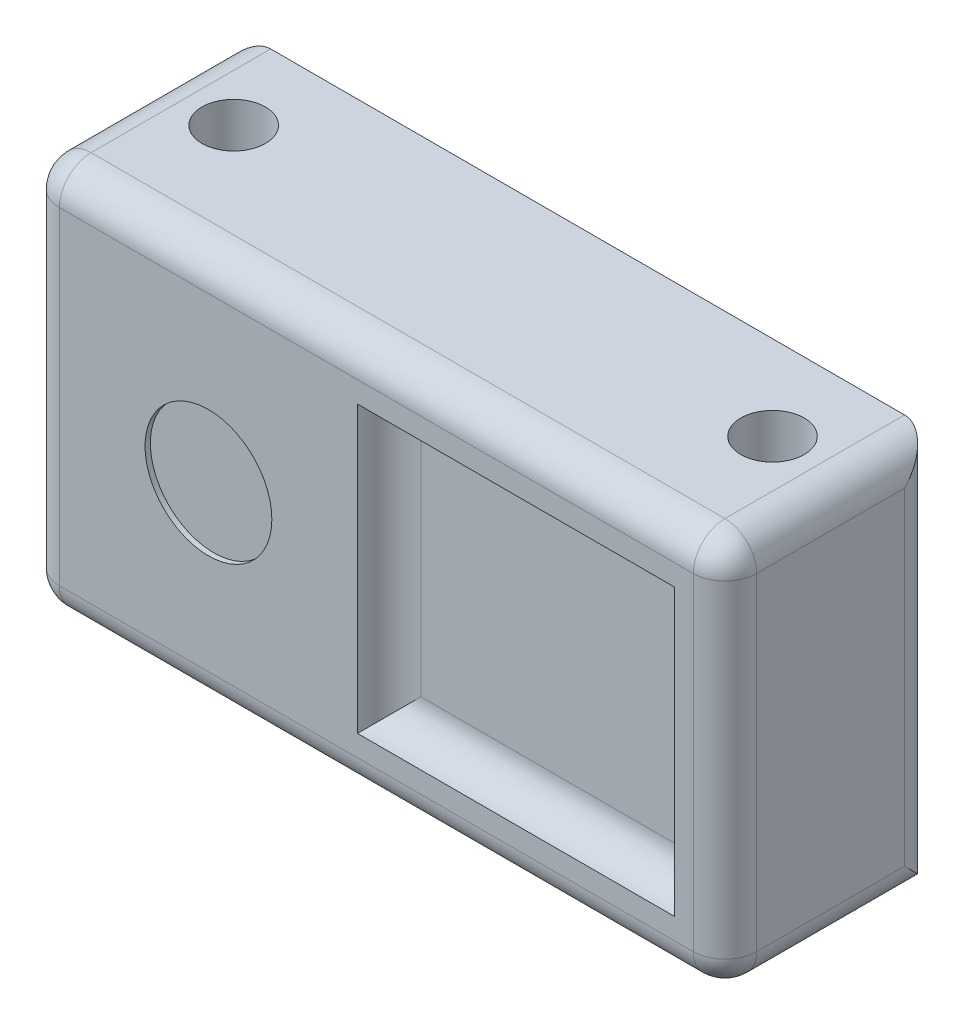
SolidWorks part; units mm, degrees
ref_plane "Ebene vorne" through (0, 0, 0) normal (0, 0, 1) x (1, 0, 0)
ref_plane "Ebene oben" through (0, 0, 0) normal (0, 1, 0) x (1, 0, 0)
ref_plane "Ebene rechts" through (0, 0, 0) normal (1, 0, 0) x (0, 0, -1)
sketch "Skizze1" plane through (0, 0, 0) normal (0, 0, 1) x (1, 0, 0)
  line L1 (-378.4567, 175.3743) -> (281.5433, 175.3743)
  line L2 (-378.4567, 175.3743) -> (-378.4567, -194.6257)
  line L3 (-378.4567, -194.6257) -> (281.5433, -194.6257)
  line L4 (281.5433, 175.3743) -> (281.5433, -194.6257)
  dimension "D1" = 660
  dimension "D2" = 370
extrude "Aufsatz-Linear austragen1" add sketch "Skizze1" along normal blind 200
sketch "Skizze2" plane through (0, -194.6257, 0) normal (0, -1, 0) x (1, 0, 0)
  line L0 (-378.4567, 200) -> (-378.4567, 0) construction
  line L1 (-378.4567, 0) -> (281.5433, 0) construction
  circle A0 centre (-303.4567, 80) radius 30
  circle A1 centre (206.5433, 80) radius 30
  dimension "D1" = 510
  dimension "D2" = 75
  dimension "D3" = 80
extrude "Schnitt-Linear austragen1" cut sketch "Skizze2" against normal through all
fillet "Verrundung1" radius 30 10 edges at (-378.4567, 175.3743, 100) (-378.4567, -9.6257, 200) (-378.4567, -194.6257, 100) (-378.4567, -9.6257, 0) (281.5433, -194.6257, 100) (281.5433, 175.3743, 100) (-48.4567, -194.6257, 200) (-48.4567, 175.3743, 200) (281.5433, -9.6257, 0) (281.5433, -9.6257, 200)
sketch "Skizze3" plane through (0, 0, 200) normal (0, 0, 1) x (1, 0, 0)
  line L0 (251.5433, -164.6257) -> (251.5433, 145.3743) construction
  line L1 (-66.2824, 125.3743) -> (233.7176, 125.3743)
  line L2 (-66.2824, 125.3743) -> (-66.2824, -144.6257)
  line L3 (-66.2824, -144.6257) -> (233.7176, -144.6257)
  line L4 (233.7176, 125.3743) -> (233.7176, -144.6257)
  line L5 (251.5433, 145.3743) -> (-348.4567, 145.3743) construction
  line L6 (-348.4567, -164.6257) -> (251.5433, -164.6257) construction
  dimension "D1" = 17.8257
  dimension "D2" = 20
  dimension "D3" = 20
  dimension "D4" = 300
extrude "Schnitt-Linear austragen2" cut sketch "Skizze3" against normal blind 30
fillet "Verrundung2" radius 30 4 edges at (233.7176, -9.6257, 170) (83.7176, -144.6257, 170) (-66.2824, -9.6257, 170) (83.7176, 125.3743, 170)
sketch "Skizze5" plane through (0, 0, 200) normal (0, 0, 1) x (1, 0, 0)
  line L0 (-348.4567, -9.6257) -> (-66.2824, -9.6257) construction
  line L1 (-348.4567, 145.3743) -> (-348.4567, -164.6257) construction
  line L2 (-66.2824, 125.3743) -> (-66.2824, -144.6257) construction
  circle A0 centre (-207.3695, -9.6257) radius 60
  point P6 (-207.3695, -9.6257)
extrude "Schnitt-Linear austragen3" cut sketch "Skizze5" against normal blind 5
